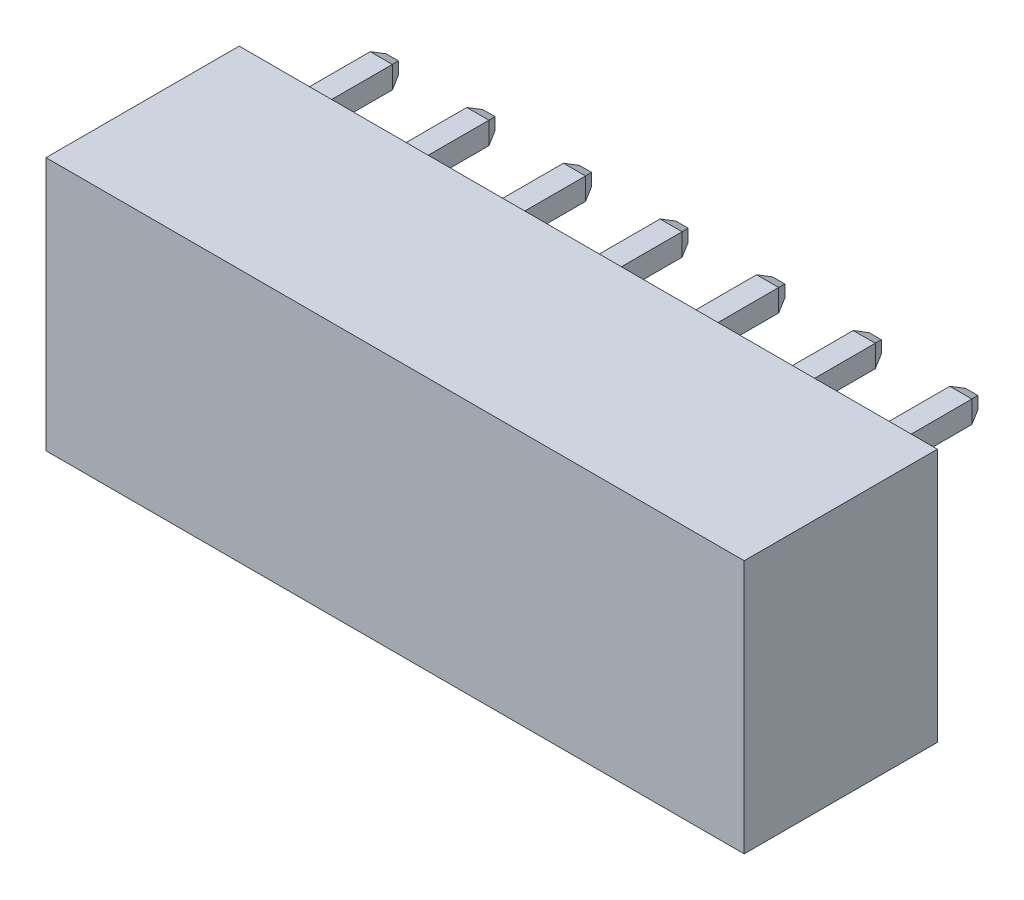
SolidWorks part; units mm, degrees
ref_plane "Спереди" through (0, 0, 0) normal (0, 0, 1) x (1, 0, 0)
ref_plane "Сверху" through (0, 0, 0) normal (0, 1, 0) x (1, 0, 0)
ref_plane "Справа" through (0, 0, 0) normal (1, 0, 0) x (0, 0, -1)
sketch "Эскиз1" plane through (0, 0, 0) normal (0, 0, 1) x (1, 0, 0)
  line L1 (12.65, 9.2) -> (-12.65, 9.2)
  line L2 (12.65, 9.2) -> (12.65, 0)
  line L3 (12.65, 0) -> (-12.65, 0)
  line L4 (-12.65, 9.2) -> (-12.65, 0)
  line L5 (12.65, 9.2) -> (-12.65, 0) construction
  line L6 (12.65, 0) -> (-12.65, 9.2) construction
  point P0 (0, 4.6)
  dimension "D1" = 9.2
  dimension "D2" = 25.3
extrude "Бобышка-Вытянуть1" add sketch "Эскиз1" along normal blind 7
sketch "Эскиз2" plane through (0, 0, 0) normal (0, 0, -1) x (-1, 0, 0)
  line L0 (12.65, 0) -> (-12.65, 0) construction
  line L1 (-10.9, 7.6) -> (-10.1, 7.6)
  line L2 (-10.9, 7.6) -> (-10.9, 8.4)
  line L3 (-10.9, 8.4) -> (-10.1, 8.4)
  line L4 (-10.1, 7.6) -> (-10.1, 8.4)
  line L5 (-10.9, 7.6) -> (-10.1, 8.4) construction
  line L6 (-10.9, 8.4) -> (-10.1, 7.6) construction
  line L7 (-12.65, 0) -> (-12.65, 9.2) construction
  point P0 (-10.5, 8)
  dimension "D1" = 8
  dimension "D2" = 0.8
  dimension "D3" = 2.15
extrude "Бобышка-Вытянуть2" add sketch "Эскиз2" along normal blind 3.4
chamfer "Фаска1" distance 0.4 angle 24 4 edges at (10.5, 8.4, -3.4) (10.1, 8, -3.4) (10.5, 7.6, -3.4) (10.9, 8, -3.4) first distance on face at (10.5, 8.4, -1.7) first distance on face at (10.1, 8, -1.7) first distance on face at (10.5, 7.6, -1.7) first distance on face at (10.9, 8, -1.7)
sketch "Эскиз3" plane through (0, 0, 0) normal (0, -1, 0) x (1, 0, 0)
  line L1 (8.9, 0.8) -> (12, 0.8)
  line L2 (8.9, 0.8) -> (8.9, 5)
  line L4 (12, 0.8) -> (12, 5)
  line L5 (8.9, 0.8) -> (12, 5) construction
  line L6 (8.9, 5) -> (12, 0.8) construction
  line L7 (-12.65, 0) -> (12.65, 0) construction
  line L9 (12.65, 7) -> (12.65, 0) construction
  line L10 (-12.65, 7) -> (12.65, 7) construction
  line L11 (8.9, 6.5) -> (12, 6.5)
  line L12 (8.9, 5) -> (9.9, 5)
  line L13 (9.9, 5) -> (8.9, 6.5)
  line L14 (12, 5) -> (11, 5)
  line L15 (11, 5) -> (12, 6.5)
  point P0 (10.45, 2.9)
  point P5 (10.45, 6.5)
  dimension "D1" = 2.2
  dimension "D2" = 0.8
  dimension "D3" = 2
  dimension "D4" = 3.1
  dimension "D5" = 0.5
  dimension "D6" = 1
extrude "Вырез-Вытянуть1" cut sketch "Эскиз3" against normal blind 7
pattern_linear "Линейный массив1" count 7 spacing 3.5 along (-1, 0, 0) of "Бобышка-Вытянуть2", "Фаска1"
pattern_linear "Линейный массив2" count 7 spacing 3.5 along (-1, 0, 0) of "Вырез-Вытянуть1"
sketch "Эскиз4" plane through (0, 7, 0) normal (0, -1, 0) x (1, 0, 0)
  line L0 (10.9, -3) -> (10.9, 0) construction
  line L1 (10.1, 3.4) -> (10.9, 3.4)
  line L2 (10.1, 3.4) -> (10.1, 2.6)
  line L3 (10.1, 2.6) -> (10.9, 2.6)
  line L4 (10.9, 3.4) -> (10.9, 2.6)
  line L5 (10.1, 3.4) -> (10.9, 2.6) construction
  line L6 (10.1, 2.6) -> (10.9, 3.4) construction
  line L7 (10.1, -3) -> (10.1, 0) construction
  line L8 (-12.65, 0) -> (12.65, 0) construction
  point P0 (10.5, 3)
  dimension "D1" = 3
extrude "Бобышка-Вытянуть3" add sketch "Эскиз4" along normal blind 6
chamfer "Фаска2" distance 0.4 angle 24 4 edges at (10.9, 1, 3) (10.5, 1, 3.4) (10.1, 1, 3) (10.5, 1, 2.6) first distance on face at (10.9, 4, 3) first distance on face at (10.5, 4, 3.4) first distance on face at (10.1, 4, 3) first distance on face at (10.5, 4, 2.6)
pattern_linear "Линейный массив3" count 7 spacing 3.5 along (-1, 0, 0) of "Фаска2", "Бобышка-Вытянуть3"
equation "\"n\"= 7"
equation "\"width\"= 3.5 * ( \"n\" - 1 ) + 4.3"
equation "\"D2@Эскиз1\" = 3.5 * ( \"n\" - 1 ) + 4.3"
equation "\"D1@Линейный массив1\"=\"n\""
equation "\"D1@Линейный массив2\"=\"n\""
equation "\"D1@Линейный массив3\"=\"n\""
